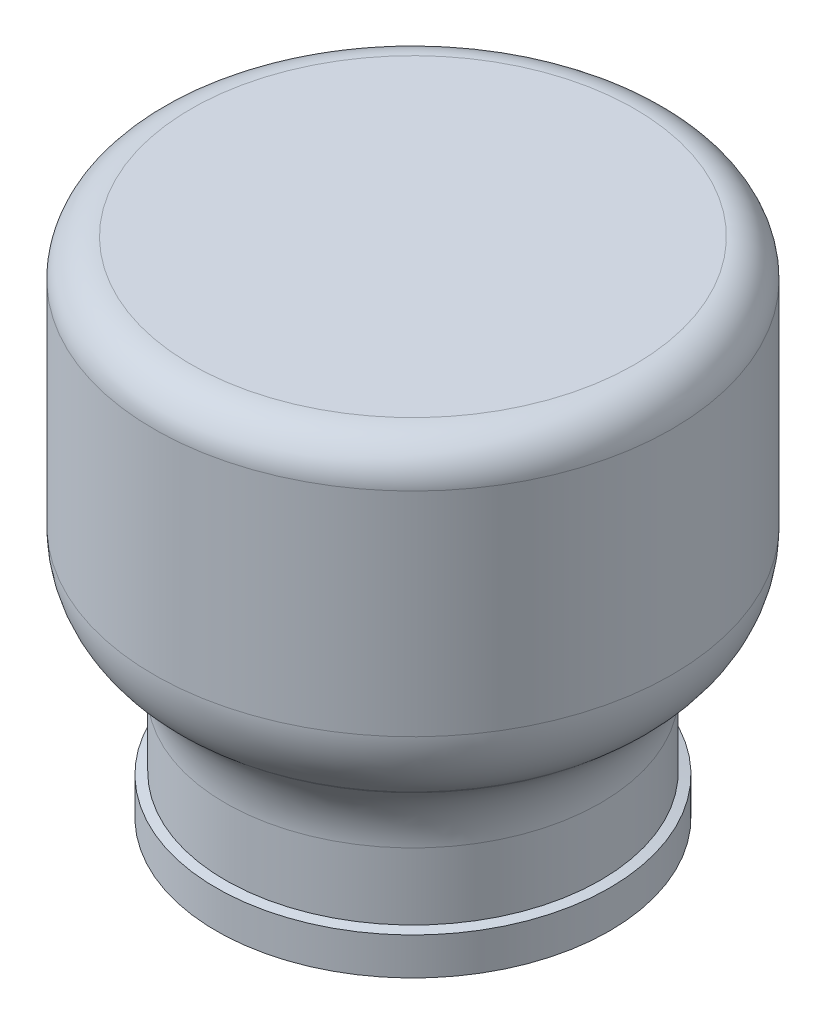
SolidWorks part; units mm, degrees
ref_plane "Front Plane" through (0, 0, 0) normal (0, 0, 1) x (1, 0, 0)
ref_plane "Top Plane" through (0, 0, 0) normal (0, 1, 0) x (1, 0, 0)
ref_plane "Right Plane" through (0, 0, 0) normal (1, 0, 0) x (0, 0, -1)
sketch "Sketch1" plane through (0, 0, 0) normal (0, 0, 1) x (1, 0, 0)
  line L0 (2.7649, 7.8218) -> (2.7649, 58.3592) construction
  line L1 (20.9, 0) -> (23.8716, 0)
  line L2 (23.8716, 0) -> (23.8716, 4)
  line L3 (23.8716, 4) -> (22.9, 4.2367)
  line L4 (22.9, 4.2367) -> (22.9, 11.4043)
  line L6 (20.9, 0) -> (20.9, 14)
  line L8 (2.7649, 52) -> (2.7649, 54)
  line L10 (17.2603, 17) -> (2.7649, 17)
  line L12 (19.9, 15) -> (2.7649, 15)
  line L13 (2.7649, 17) -> (2.7649, 15)
  line L15 (23.6882, 19.3396) -> (24.9883, 20.4305)
  line L16 (28.5604, 28.091) -> (28.5604, 50)
  line L17 (26.4721, 19.0648) -> (26.9883, 19.4979)
  line L18 (30.5604, 27.1583) -> (30.5604, 50)
  line L19 (26.5604, 52) -> (2.7649, 52)
  line L20 (26.5604, 54) -> (2.7649, 54)
  arc A0 (28.5604, 50) -> (26.5604, 52) centre (26.5604, 50) ccw
  arc A1 (30.5604, 50) -> (26.5604, 54) centre (26.5604, 50) ccw
  arc A2 (26.4721, 19.0648) -> (22.9, 11.4043) centre (32.9, 11.4043) ccw
  arc A3 (26.9883, 19.4979) -> (30.5604, 27.1583) centre (20.5604, 27.1583) ccw
  arc A4 (24.9883, 20.4305) -> (28.5604, 28.091) centre (18.5604, 28.091) ccw
  arc A5 (17.2603, 17) -> (23.6882, 19.3396) centre (17.2603, 27) ccw
  arc A6 (20.9, 14) -> (19.9, 15) centre (19.9, 14) ccw
  point P11 (22.9, 54)
  point P28 (28.5604, 23.4279)
  point P31 (20.9, 17)
  dimension "D8" = 2
  dimension "D9" = 4
  dimension "D4" = 2
  dimension "D16" = 10
  dimension "D17" = 10
  dimension "D18" = 10
  dimension "D19" = 1
  dimension "D1" = 2
  dimension "D2" = 4
  dimension "D3" = 1
  dimension "D5" = 140
  dimension "D6" = 2
  dimension "D7" = 2.9716
  dimension "D10" = 2
  dimension "D11" = 15
  dimension "D12" = 35
  dimension "D13" = 37
  dimension "D14" = 2
  dimension "D15" = 10
revolve "Revolve1" add sketch "Sketch1" angle 360 about L0
ref_plane "Plane1" through (0, 4, 0) normal (0, 1, 0) x (1, 0, 0)
sketch "Sketch3" plane through (0, 0, 0) normal (0, 0, 1) x (1, 0, 0)
  point P0 (1.2404, 19.1989)
ref_point "Point1"
ref_plane "Plane2" through (0, 0, 22.9) normal (0, 0, 1) x (1, 0, 0)
sketch "Sketch4" plane through (0, 0, 22.9) normal (0, 0, 1) x (1, 0, 0)
  line L1 (22.9, 51) -> (-17.3702, 51) construction
  circle A1 centre (1.1446, 39) radius 10
  dimension "D1" = 20
  dimension "D2" = 12
extrude "Boss-Extrude2" add sketch "Sketch4" against normal blind 6
ref_plane "Plane3" through (0, 0, 16.9) normal (0, 0, -1) x (-1, 0, 0)
ref_plane "Plane4" through (0, 54, 0) normal (0, 1, 0) x (1, 0, 0)
sketch "Sketch9" plane through (0, 54, 0) normal (0, 1, 0) x (1, 0, 0)
  line L0 (-14.7351, -0.0013) -> (20.2649, -0.0013)
  arc A0 (20.2649, -0.0013) -> (-14.7351, -0.0013) centre (2.7649, -0.0013) ccw
  circle A1 centre (2.7649, 0) radius 17.1351 construction
  dimension "D1" = 35
  dimension "D3" = 17.5
  dimension "D2" = 17.5
extrude "Cut-Extrude2" cut sketch "Sketch9" against normal blind 40 rebuild error yes
